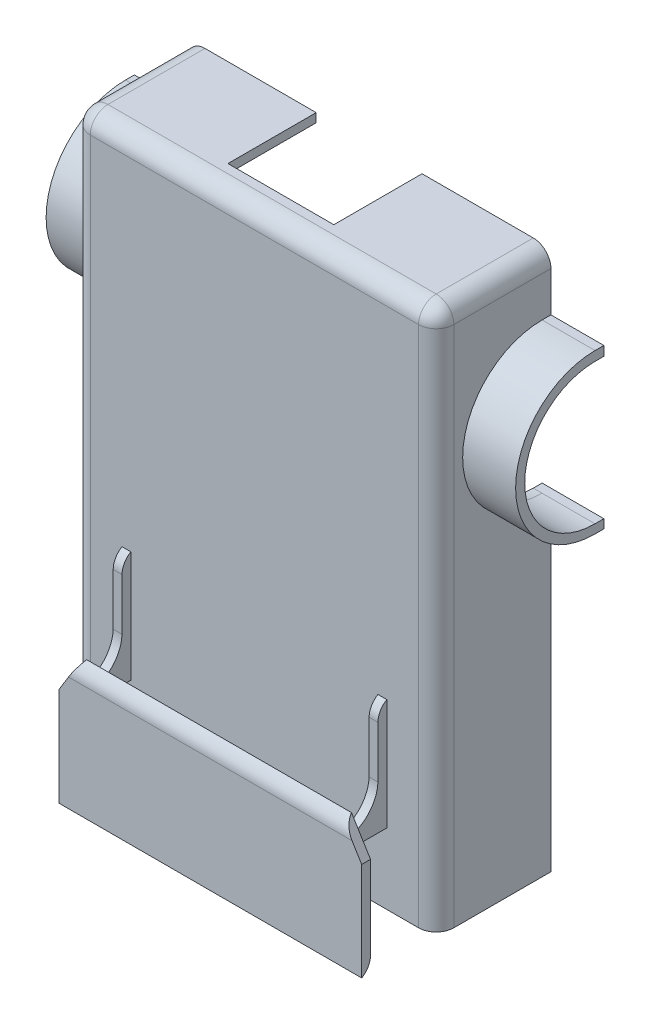
SolidWorks part; units mm, degrees
ref_plane "정면" through (0, 0, 0) normal (0, 0, 1) x (1, 0, 0)
ref_plane "윗면" through (0, 0, 0) normal (0, 1, 0) x (1, 0, 0)
ref_plane "우측면" through (0, 0, 0) normal (1, 0, 0) x (0, 0, -1)
sketch "Sketch1" plane through (0, 0, 0) normal (0, 0, 1) x (1, 0, 0)
  line L0 (103, -103) -> (-103, -103)
  line L1 (-103, -103) -> (-103, 203)
  line L2 (-103, 203) -> (103, 203)
  line L3 (0, -202.1962) -> (0, 360.5295) construction
  line L4 (103, -103) -> (103, 203)
  point P2 (0, -83.194)
  point P7 (0, -106.8821)
  point P8 (0, 0)
  point P9 (14.426, -106.8821)
  point P10 (0, 0)
  point P11 (0, 0)
  point P12 (-21.5828, -106.8821)
  point P13 (0, 0)
  point P14 (-0.7666, -202.1962)
  point P17 (0, 203)
  point P18 (0, -103)
  dimension "D1" = 103
  dimension "D2" = 306
  dimension "D3" = 103
extrude "Boss-Extrude2" add sketch "Sketch1" along normal blind 5
sketch "Sketch2" plane through (0, 0, 0) normal (0, 0, -1) x (-1, 0, 0)
  line L0 (0, -214.0289) -> (0, 295.0441) construction
  line L1 (103, -103) -> (-103, -103)
  line L2 (103, -103) -> (-103, -103) construction
  line L3 (-103, -103) -> (-103, 203)
  line L4 (-103, 203) -> (103, 203) construction
  line L5 (-103, -103) -> (-103, 203) construction
  line L6 (-103, 203) -> (103, 203)
  line L7 (0, 203) -> (0, 198)
  line L8 (98, 198) -> (-98, 198)
  line L9 (-98, 198) -> (-98, -98)
  line L10 (-98, -98) -> (98, -98)
  line L11 (0, -98) -> (0, -103)
  line L12 (98, 198) -> (98, -98)
  line L13 (103, -103) -> (103, 203)
  dimension "D1" = 98
  dimension "D2" = 98
  dimension "D3" = 296
extrude "Boss-Extrude3" add sketch "Sketch2" along normal blind 60 contours L11 L10 L9 L8 L7 L6 L1 L0 | L8 L12 L10 L11 L1 L6 L7 region at (-49, -101.2287, 0) region at (3.2287, -100.5, 0)
sketch "Sketch3" plane through (0, 0, 0) normal (0, 0, -1) x (-1, 0, 0)
  line L0 (0, -201.4115) -> (0, 296.0467) construction
  line L1 (-50, -98) -> (-50, 100)
  line L2 (-98, -98) -> (98, -98) construction
  line L3 (-50, 100) -> (-55, 100)
  line L4 (-55, 100) -> (-55, -98)
  line L5 (-55, -98) -> (-50, -98)
  line L6 (55, -98) -> (50, -98)
  line L7 (55, 100) -> (55, -98)
  line L8 (50, 100) -> (55, 100)
  line L9 (50, -98) -> (50, 100)
  dimension "D1" = 50
  dimension "D2" = 5
  dimension "D3" = 198
extrude "Boss-Extrude4" add sketch "Sketch3" along normal blind 60
sketch "Sketch10" plane through (0, 0, -60) normal (0, 0, -1) x (-1, 0, 0)
  line L0 (0, -135.3908) -> (0, 274.3287) construction
  line L1 (30, 198) -> (-30, 198)
  line L2 (98, 198) -> (-98, 198) construction
  line L3 (-30, 198) -> (-30, 203)
  line L4 (103, 203) -> (-103, 203) construction
  line L5 (-30, 203) -> (30, 203)
  line L6 (30, 198) -> (30, 203)
  point P12 (0, 203)
  point P13 (0, 198)
  dimension "D1" = 30
extrude "Cut-Extrude3" cut sketch "Sketch10" against normal blind 50
sketch "Sketch11" plane through (103, 0, 0) normal (1, 0, 0) x (0, 0, -1)
  line L0 (0, -127.7341) -> (0, 279.3891) construction
  line L1 (-5, -127.7341) -> (-5, 406.1734) construction
  line L2 (55, -136.4391) -> (55, 386.9331) construction
  line L3 (-5, 198) -> (50, 198) construction
  line L4 (-5, 203) -> (60, 203) construction
  line L5 (55, 165.247) -> (60, 165.247)
  line L6 (60, 203) -> (60, -103) construction
  line L7 (60, 165.247) -> (60, 85.247)
  line L8 (60, 85.247) -> (55, 85.247)
  line L9 (60, -122.2925) -> (60, 246.4878) construction
  arc A0 (55, 165.247) -> (55, 85.247) centre (55, 125.247) ccw
  dimension "D2" = 5
  dimension "D3" = 5
  dimension "D1" = 5
extrude "Cut-Extrude4" cut sketch "Sketch11" against normal blind 5 and the other way through all
sketch "Sketch12" plane through (103, 0, 0) normal (1, 0, 0) x (0, 0, -1)
  line L0 (55, 274.0718) -> (55, -200.485) construction
  line L1 (60, 265.5367) -> (60, -179.5347) construction
  line L2 (-27.4602, 203) -> (90.9278, 203) construction
  line L3 (0, -200.485) -> (0, 274.0718) construction
  line L4 (55, 170.247) -> (60, 170.247)
  line L5 (60, 170.247) -> (60, 164.9224)
  line L6 (60, 164.9224) -> (55, 164.9224)
  line L7 (55, 85.247) -> (60, 85.247)
  line L8 (60, 85.247) -> (60, 80.247)
  line L9 (60, 80.247) -> (55, 80.247)
  arc A3 (55, 170.247) -> (55, 80.247) centre (55, 125.247) ccw
  arc A4 (55, 170.247) -> (55, 80.247) centre (55, 125.247) ccw
  arc A5 (55, 164.9224) -> (55, 85.247) centre (55, 125.0847) ccw
  dimension "D1" = 60
  dimension "D2" = 5
  dimension "D3" = 5
extrude "Boss-Extrude6" add sketch "Sketch12" along normal blind 30
sketch "Sketch13" plane through (-103, 0, 0) normal (-1, 0, 0) x (0, 0, 1)
  line L0 (0, -36.1559) -> (0, 92.375) construction
  line L1 (5, -55.4355) -> (5, 249.3092) construction
  line L2 (5, 203) -> (5, -103) construction
  line L3 (-60, -55.4355) -> (-60, 246.5799) construction
  line L4 (-60, -103) -> (-60, 203) construction
  line L5 (-90.2482, 203) -> (66.5207, 203) construction
  line L7 (-55, 246.5799) -> (-55, -169.3005) construction
  line L8 (-55, 165) -> (-60, 165)
  line L9 (-60, 165) -> (-60, 85)
  line L10 (-60, 85) -> (-55, 85)
  arc A1 (-55, 165) -> (-55, 85) centre (-55, 125) cw
  point P15 (-55, 125)
  point P16 (-60, 125)
  dimension "D1" = 78
  dimension "D2" = 5
extrude "Cut-Extrude5" cut sketch "Sketch13" against normal blind 5 and the other way through all
sketch "Sketch14" plane through (-103, 0, 0) normal (-1, 0, 0) x (0, 0, 1)
  line L0 (0, -35.5451) -> (0, 219.6348) construction
  line L1 (-60, -56.9755) -> (-60, 219.6348) construction
  line L2 (-60, -103) -> (-60, 85) construction
  line L3 (5, 203) -> (-60, 203) construction
  line L8 (-55, 219.6348) -> (-55, -170.9077) construction
  line L9 (-55, 170) -> (-60, 170)
  line L10 (-60, 170) -> (-60, 165)
  line L11 (-60, 165) -> (-55, 165)
  line L12 (-55, 85) -> (-60, 85)
  line L13 (-60, 85) -> (-60, 80)
  line L14 (-60, 80) -> (-55, 80)
  arc A6 (-55, 165) -> (-55, 85) centre (-55, 125) cw
  arc A7 (-55, 80) -> (-55, 170) centre (-55, 125) ccw
  arc A8 (-55, 80) -> (-55, 170) centre (-55, 125) ccw
  point P7 (-60, 125)
  dimension "D1" = 78
  dimension "D2" = 5
  dimension "D3" = 5
extrude "Boss-Extrude7" add sketch "Sketch14" along normal blind 30
sketch "Sketch16" plane through (0, 0, 5) normal (0, 0, 1) x (1, 0, 0)
  line L0 (0, -119.7009) -> (0, 255.0389) construction
  line L1 (-181.9033, -63) -> (211.4012, -63) construction
  line L2 (-103, -103) -> (103, -103) construction
  line L3 (-75, -63) -> (-75, 0)
  line L4 (-75, 0) -> (-70, 0)
  line L5 (-70, 0) -> (-70, -63)
  line L6 (-70, -63) -> (-75, -63)
  line L7 (70, -63) -> (75, -63)
  line L8 (70, 0) -> (70, -63)
  line L9 (75, 0) -> (70, 0)
  line L10 (75, -63) -> (75, 0)
  dimension "D1" = 40
  dimension "D2" = 70
  dimension "D3" = 75
  dimension "D4" = 63
extrude "Boss-Extrude8" add sketch "Sketch16" along normal blind 5
sketch "Sketch17" plane through (-75, 0, 0) normal (-1, 0, 0) x (0, 0, 1)
  line L0 (5, -72.557) -> (5, 7.1974) construction
  line L1 (5, 203) -> (5, -103) construction
  line L2 (30, -79.9525) -> (30, -5.9365) construction
  line L3 (68.5418, -63) -> (-63.6559, -63) construction
  line L4 (5, -63) -> (30, -63)
  line L5 (96.528, -38) -> (-29.9007, -38) construction
  line L6 (30, -63) -> (30, -57.184)
  line L7 (10, 0) -> (10, -63) construction
  line L8 (10, -38) -> (10, 0)
  line L9 (10, 0) -> (5, 0)
  line L10 (5, 0) -> (5, -63)
  arc A0 (30, -57.184) -> (10, -38) centre (30, -37.1667) cw
  dimension "D1" = 25
  dimension "D2" = 25
extrude "Boss-Extrude10" add sketch "Sketch17" against normal blind 150
sketch "Sketch19" plane through (0, -63, 0) normal (0, -1, 0) x (1, 0, 0)
  line L0 (0, -20.3946) -> (0, 70.3946) construction
  line L1 (-111.1094, 5) -> (115.0967, 5) construction
  line L2 (70, 25) -> (-70, 25)
  line L3 (-70, 25) -> (-70, 5)
  line L4 (-70, 5) -> (70, 5)
  line L5 (75, 30) -> (-75, 30) construction
  line L6 (-75, 30) -> (-75, 5) construction
  line L7 (70, 25) -> (70, 5)
  point P15 (0, 5)
  point P16 (0, 25)
  dimension "D1" = 5
  dimension "D2" = 5
extrude "Cut-Extrude6" cut sketch "Sketch19" against normal blind 70 from surface starting at face at (0, -63, 17.5)
sketch "Sketch20" plane through (0, 0, 30) normal (0, 0, 1) x (1, 0, 0)
  line L0 (0, -171.7948) -> (0, 11.7269) construction
  line L1 (75, -45.4396) -> (-75, -45.4396)
  line L2 (-75, 0) -> (-75, -38) construction
  line L3 (-75, -45.4396) -> (-85.7928, -63)
  line L4 (-85.7928, -63) -> (-85.7928, -118.7167)
  line L5 (-85.7928, -118.7167) -> (85.7928, -118.7167)
  line L6 (85.7928, -63) -> (85.7928, -118.7167)
  line L7 (75, -45.4396) -> (85.7928, -63)
  point P11 (0, -89.257)
  point P12 (0, -18.6077)
  point P13 (0, -118.7167)
  point P14 (0, -45.4396)
extrude "Boss-Extrude11" add sketch "Sketch20" against normal blind 5
fillet "Fillet3" radius 10 1 edges at (-103, 203, -27.5)
fillet "Fillet4" radius 10 1 edges at (103, 203, -27.5)
fillet "Fillet5" radius 10 1 edges at (0, -45.4396, 30)
fillet "Fillet6" radius 10 1 edges at (0, -118.7167, 25)
fillet "Fillet7" radius 10 1 edges at (-72.5, 0, 10)
fillet "Fillet8" radius 10 1 edges at (72.5, 0, 10)
fillet "Fillet9" radius 10 5 edges at (103, 45, 5) (-103, 45, 5) (-100.0711, 200.0711, 5) (0, 203, 5) (100.0711, 200.0711, 5)
